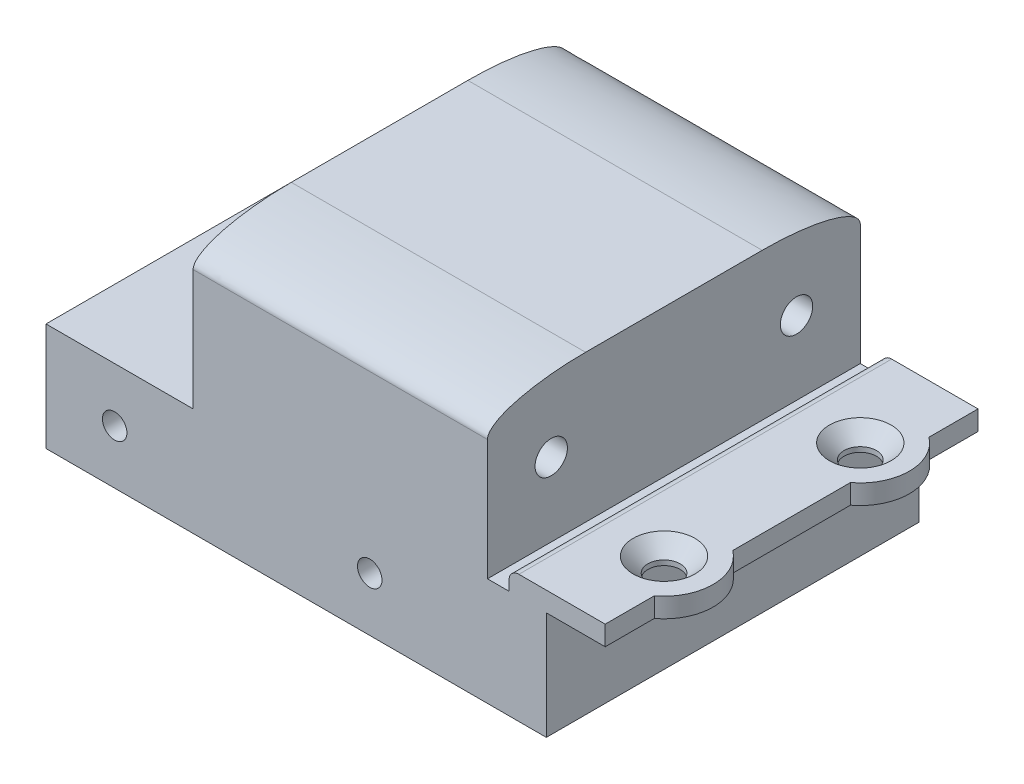
SolidWorks part; units mm, degrees
ref_plane "Спереди" through (0, 0, 0) normal (0, 0, 1) x (1, 0, 0)
ref_plane "Сверху" through (0, 0, 0) normal (0, 1, 0) x (1, 0, 0)
ref_plane "Справа" through (0, 0, 0) normal (1, 0, 0) x (0, 0, -1)
sketch "Эскиз6" [suppressed] plane through (0, 0, 0) normal (0, 1, 0) x (1, 0, 0)
  line L0 (-20, 0) -> (31, 0) construction
  line L1 (-20, -19) -> (31, -19)
  line L2 (-20, -19) -> (-20, 19)
  line L3 (-20, 19) -> (31, 19)
  line L4 (31, -19) -> (31, 19)
  line L5 (0, -19) -> (0, 19) construction
  dimension "D1" = 31
  dimension "D2" = 20
  dimension "D3" = 38
extrude "тело" [suppressed] add sketch "Эскиз6" along normal blind 11
sketch "Эскиз10" [suppressed] plane through (0, 11, 0) normal (0, 1, 0) x (1, 0, 0)
  circle A0 centre (0, 0) radius 10
  dimension "D1" = 20
extrude "основание оси" [suppressed] add sketch "Эскиз10" along normal blind 3
fillet "Скругление1" [suppressed] radius 3
sketch "Эскиз13" [suppressed] plane through (0, 0, 19) normal (0, 0, 1) x (1, 0, 0)
  line L0 (31, 5.5) -> (-13, 5.5) construction
  line L1 (31, 11) -> (31, 0) construction
  line L2 (0, 0) -> (0, 11) construction
  line L3 (-20, 11) -> (31, 11) construction
  circle A0 centre (-13, 5.5) radius 1.25
  circle A1 centre (13, 5.5) radius 1.25
  dimension "D1" = 2.5
  dimension "D2" = 26
  dimension "D3" = 18
extrude "отверстия под шурупы" [suppressed] cut sketch "Эскиз13" against normal through all
sketch "Эскиз15" [suppressed] plane through (0, 14, 0) normal (0, 1, 0) x (1, 0, 0)
  circle A0 centre (0, 0) radius 8.65
  dimension "D1" = 17.3
extrude "ось" [suppressed] add sketch "Эскиз15" along normal blind 13
sketch "Эскиз16" [suppressed] plane through (0, 27, 0) normal (0, 1, 0) x (1, 0, 0)
  line L0 (-7, 1.65) -> (-8.4912, 1.65) construction
  line L1 (-7, -1.65) -> (-8.4912, -1.65) construction
  line L2 (-1.65, 7) -> (-1.65, 8.4912)
  line L3 (1.65, 7) -> (1.65, 8.4912)
  line L4 (7, 1.65) -> (8.4912, 1.65) construction
  line L5 (7, -1.65) -> (8.4912, -1.65) construction
  line L6 (1.65, -7) -> (1.65, -8.4912)
  line L8 (-1.65, -7) -> (-1.65, -8.4912)
  circle A0 centre (0, 0) radius 7 construction
  arc A1 (-1.65, 7) -> (1.65, 7) centre (0, 7) ccw
  arc A2 (7, 1.65) -> (7, -1.65) centre (7, 0) ccw construction
  arc A3 (1.65, -7) -> (-1.65, -7) centre (0, -7) ccw
  arc A4 (-7, -1.65) -> (-7, 1.65) centre (-7, 0) ccw construction
  arc A5 (-8.4912, 1.65) -> (-8.4912, -1.65) centre (0, 0) ccw construction
  circle A6 centre (0, 0) radius 8.65 construction
  arc A7 (1.65, 8.4912) -> (-1.65, 8.4912) centre (0, 0) ccw
  arc A8 (8.4912, -1.65) -> (8.4912, 1.65) centre (0, 0) ccw construction
  arc A9 (-1.65, -8.4912) -> (1.65, -8.4912) centre (0, 0) ccw
  dimension "D1" = 14
  dimension "D2" = 1.65
extrude "крепление к серве" [suppressed] cut sketch "Эскиз16" against normal up to surface (13 mm away)
sketch "Эскиз26" [suppressed] plane through (0, 14, 0) normal (0, 1, 0) x (1, 0, 0)
  circle A0 centre (0, 7) radius 1.65
  circle A1 centre (0, -7) radius 1.65
  arc A2 (1.65, -7) -> (-1.65, -7) centre (0, -7) ccw construction
extrude "продолжение креплений" [suppressed] cut sketch "Эскиз26" against normal through all
chamfer "Фаска7" [suppressed] distance 2 angle 45
sketch "Эскиз17" [suppressed] plane through (0, 27, 0) normal (0, 1, 0) x (1, 0, 0)
  circle A0 centre (0, 0) radius 3
  dimension "D1" = 6
extrude "отверстие под болтик" [suppressed] cut sketch "Эскиз17" against normal through all
sketch "Эскиз24" [suppressed] plane through (0, 11, 0) normal (0, 1, 0) x (1, 0, 0)
  line L0 (31, 19) -> (-20, 19) construction
  line L1 (-15, 19) -> (15, 19)
  line L2 (-15, 19) -> (-15, -19)
  line L3 (-15, -19) -> (15, -19)
  line L4 (15, 19) -> (15, -19)
  line L5 (-20, -19) -> (31, -19) construction
  line L6 (0, 19) -> (0, -19) construction
  dimension "D1" = 30
extrude "крепление к арке" [suppressed] add sketch "Эскиз24" along normal blind 15
sketch "Эскиз27" [suppressed] plane through (-15, 0, 0) normal (-1, 0, 0) x (0, 0, 1)
  line L0 (0, 11) -> (0, 26) construction
  line L1 (-19, 11) -> (19, 11) construction
  line L2 (-19, 26) -> (19, 26) construction
  line L3 (-12.5, 18.5) -> (12.5, 18.5) construction
  circle A0 centre (-12.5, 18.5) radius 1.65
  circle A1 centre (12.5, 18.5) radius 1.65
  dimension "D2" = 3.3
  dimension "D1" = 25
  dimension "D3" = 7.5
extrude "отверстия под болты" [suppressed] cut sketch "Эскиз27" against normal through all
sketch "Эскиз19" [suppressed] plane through (0, 11, 0) normal (0, 1, 0) x (1, 0, 0)
  line L0 (15, -19) -> (31, -19) construction
  line L1 (37, 19) -> (23, 19)
  line L2 (37, 19) -> (37, -19)
  line L3 (37, -19) -> (23, -19)
  line L4 (23, 19) -> (23, -19)
  line L5 (31, 19) -> (31, -19) construction
  line L6 (31, -19) -> (31, 19) construction
  dimension "D1" = 6
  dimension "D2" = 8
extrude "выступ прикрутиться к колену" [suppressed] add sketch "Эскиз19" along normal blind 2
sketch "Эскиз20" [suppressed] plane through (0, 13, 0) normal (0, 1, 0) x (1, 0, 0)
  line L0 (34, 19) -> (34, -19) construction
  line L1 (37, 19) -> (23, 19) construction
  line L2 (23, -19) -> (37, -19) construction
  line L3 (37, -19) -> (37, 19) construction
  line L4 (23, 0) -> (37, 0) construction
  line L5 (23, 19) -> (23, -19) construction
  circle A0 centre (34, 10) radius 1.65
  circle A1 centre (34, -10) radius 1.65
  dimension "D3" = 3.3
  dimension "D1" = 3
  dimension "D2" = 20
extrude "шурупы сверху" [suppressed] cut sketch "Эскиз20" against normal through all
sketch "Эскиз23" [suppressed] plane through (0, 13, 0) normal (0, 1, 0) x (1, 0, 0)
  circle A0 centre (34, 10) radius 5
  circle A1 centre (34, -10) radius 5
  circle A2 centre (34, 10) radius 1.65
  circle A3 centre (34, -10) radius 1.65
  circle A4 centre (34, -10) radius 1.65 construction
  circle A5 centre (34, 10) radius 1.65 construction
  dimension "D1" = 10
extrude "наплывы" [suppressed] add sketch "Эскиз23" against normal up to surface (2 mm away)
chamfer "Фаска4" [suppressed] distance 1 angle 45
fillet "Скругление7" [suppressed] radius 3
chamfer "Фаска6" [suppressed] distance 1.5 angle 45
fillet "Скругление8" [suppressed] radius 0.5
sketch "Эскиз28" plane through (0, 0, 0) normal (0, 0, 1) x (1, 0, 0)
  line L0 (25.5, 0) -> (25.5, 11)
  line L1 (25.5, 11) -> (31.5, 11)
  line L2 (31.5, 11) -> (31.5, 13)
  line L3 (31.5, 13) -> (22.7, 13)
  line L5 (21.7, 11) -> (19.5, 11)
  line L6 (19.5, 11) -> (19.5, 26)
  line L7 (19.5, 26) -> (-10.5, 26)
  line L8 (-10.5, 26) -> (-10.5, 11)
  line L9 (-10.5, 11) -> (-25.5, 11)
  line L10 (-25.5, 11) -> (-25.5, 0)
  line L11 (-25.5, 0) -> (25.5, 0)
  line L12 (21.7, 12) -> (21.7, 11)
  arc A0 (22.7, 13) -> (21.7, 12) centre (22.7, 12) ccw
  circle A1 centre (7.5, 5.5) radius 1.25
  circle A2 centre (-18.5, 5.5) radius 1.25
  point P6 (0, 0)
  point P15 (0, 0)
  dimension "D6" = 1
  dimension "D9" = 2.5
  dimension "D1" = 15
  dimension "D2" = 30
  dimension "D3" = 6
  dimension "D4" = 51
  dimension "D5" = 2
  dimension "D7" = 11
  dimension "D8" = 26
  dimension "D10" = 5.5
  dimension "D11" = 6
  dimension "D12" = 2.2
  dimension "D13" = 18
extrude "Основа" add sketch "Эскиз28" along normal blind 38
sketch "Эскиз29" plane through (-10.5, 0, 0) normal (-1, 0, 0) x (0, 0, 1)
  line L0 (38, 26) -> (0, 26) construction
  line L1 (6.5, 18.5) -> (31.5, 18.5) construction
  circle A0 centre (6.5, 18.5) radius 1.65
  circle A1 centre (31.5, 18.5) radius 1.65
  point P4 (19, 18.5)
  point P5 (19, 26)
  dimension "D1" = 3.3
  dimension "D2" = 7.5
  dimension "D3" = 25
extrude "Отверстия под болты крепления к арке" cut sketch "Эскиз29" against normal up to next
sketch "Эскиз30" plane through (0, 13, 0) normal (0, 1, 0) x (1, 0, 0)
  line L0 (31.5, -38) -> (31.5, 0) construction
  line L1 (28.5, -29) -> (28.5, -9) construction
  circle A0 centre (28.5, -9) radius 1.65
  circle A1 centre (28.5, -29) radius 1.65
  point P4 (28.5, -19)
  point P7 (31.5, -19)
  dimension "D2" = 3.3
  dimension "D1" = 20
  dimension "D3" = 3
extrude "Отверстия под шурупы сверху" cut sketch "Эскиз30" against normal up to next
sketch "Эскиз31" plane through (0, 13, 0) normal (0, 1, 0) x (1, 0, 0)
  line L0 (31.5, -5) -> (31.5, -13)
  line L1 (31.5, -33) -> (31.5, -25)
  line L2 (31.5, -38) -> (31.5, 0) construction
  arc A0 (31.5, -13) -> (31.5, -5) centre (28.5, -9) ccw
  arc A1 (31.5, -33) -> (31.5, -25) centre (28.5, -29) ccw
  point P12 (0, 0)
  point P13 (0, 0)
  dimension "D1" = 10
extrude "Наплывы под шурупы сверху" add sketch "Эскиз31" against normal up to surface (2 mm away) up to face at (28.5, 11, 10.65)
chamfer "Фаска8" distance 1.5 angle 45 2 edges at (26.85, 13, 29) (26.85, 13, 9)
fillet "Скругление9" radius 2.7 1 edges at (4.5, 26, 0) second distance 10 first distance on face at (11.2995, 12.0159, 0)
fillet "Скругление10" radius 10 1 edges at (4.5, 26, 38) second distance 2.7 first distance on face at (8.25, 26, 31)
